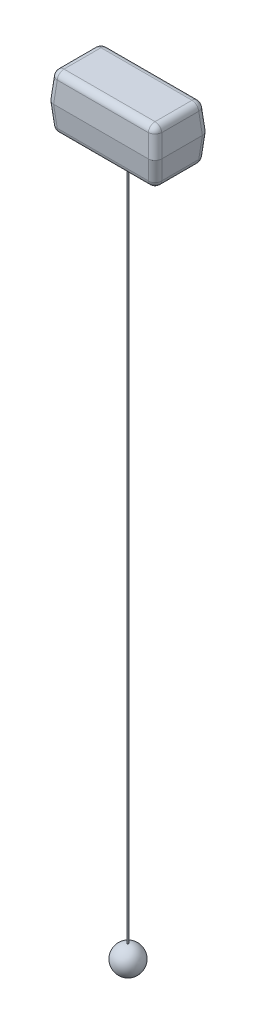
SolidWorks part; units mm, degrees
material "Nylon 101"
ref_plane "Front Plane" through (0, 0, 0) normal (0, 0, 1) x (1, 0, 0)
ref_plane "Top Plane" through (0, 0, 0) normal (0, 1, 0) x (1, 0, 0)
ref_plane "Right Plane" through (0, 0, 0) normal (1, 0, 0) x (0, 0, -1)
sketch "Sketch1" plane through (0, 0, 0) normal (0, 1, 0) x (1, 0, 0)
  line L1 (-50.8, -25.4) -> (50.8, -25.4)
  line L2 (-50.8, -25.4) -> (-50.8, 25.4)
  line L3 (-50.8, 25.4) -> (50.8, 25.4)
  line L4 (50.8, -25.4) -> (50.8, 25.4)
  line L5 (-50.8, -25.4) -> (50.8, 25.4) construction
  line L6 (-50.8, 25.4) -> (50.8, -25.4) construction
  point P0 (0, 0)
  dimension "D1" = 101.6
  dimension "D2" = 50.8
extrude "Boss-Extrude1" add sketch "Sketch1" along normal mid plane 50.8 draft 5
fillet "Fillet1" radius 6.35 16 edges at (-48.5778, -25.4, 0) (0, -25.4, 23.1778) (49.6889, 12.7, 24.2889) (49.6889, 12.7, -24.2889) (-49.6889, 12.7, -24.2889) (-49.6889, 12.7, 24.2889) (48.5778, 25.4, 0) (0, 25.4, -23.1778) (-48.5778, 25.4, 0) (0, 25.4, 23.1778) (48.5778, -25.4, 0) (0, -25.4, -23.1778) (49.6889, -12.7, 24.2889) (-49.6889, -12.7, 24.2889) (-49.6889, -12.7, -24.2889) (49.6889, -12.7, -24.2889)
sketch "Sketch2" plane through (0, -25.4, 0) normal (0, -1, 0) x (1, 0, 0)
  circle A0 centre (0, 0) radius 0.635
  dimension "D1" = 1.27
extrude "Boss-Extrude2" add sketch "Sketch2" along normal blind 660.4 separate body
sketch "Sketch3" plane through (0, 0, 0) normal (0, 0, 1) x (1, 0, 0)
  line L0 (0, -685.8) -> (0, -673.1) construction
  line L1 (-0.635, -685.8) -> (0.635, -685.8) construction
  line L2 (0, -673.1) -> (0, -698.5)
  arc A0 (0, -673.1) -> (0, -698.5) centre (0, -685.8) cw
  dimension "D1" = 12.7
revolve "Revolve1" add sketch "Sketch3" angle 360 about L0
